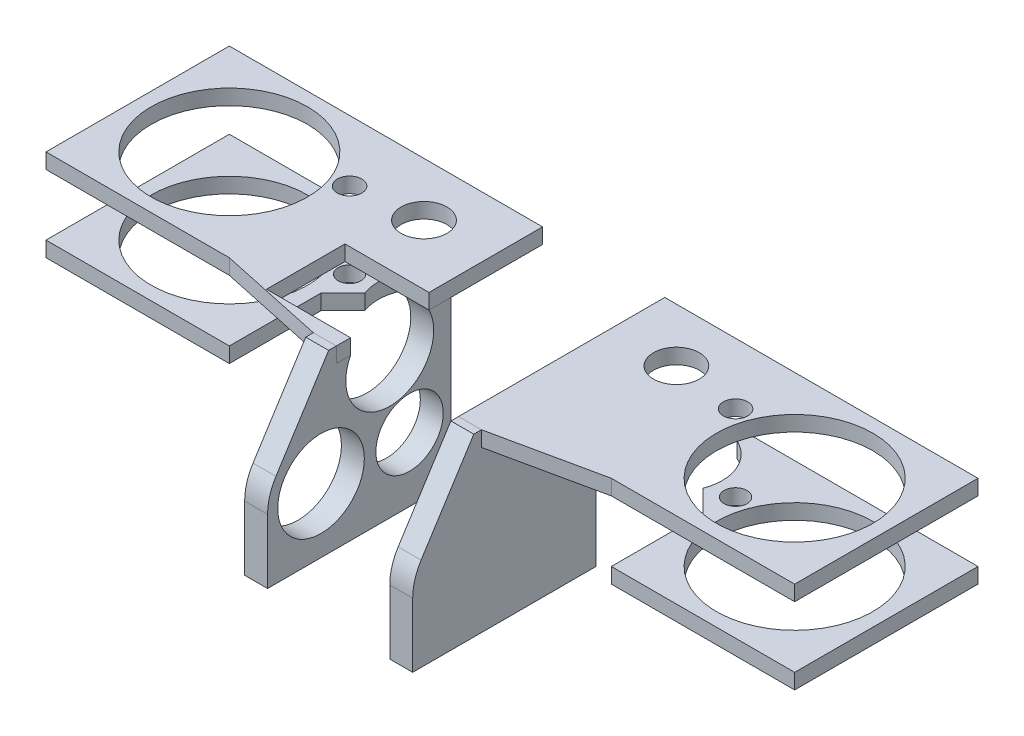
SolidWorks part; units mm, degrees
material "Alum Plate"
ref_plane "Front Plane" through (0, 0, 0) normal (0, 0, 1) x (1, 0, 0)
ref_plane "Top Plane" through (0, 0, 0) normal (0, 1, 0) x (1, 0, 0)
ref_plane "Right Plane" through (0, 0, 0) normal (1, 0, 0) x (0, 0, -1)
sketch "Sketch1" plane through (0, 0, 0) normal (0, 1, 0) x (1, 0, 0)
  line L0 (0, 0) -> (117.475, 0) construction
  line L1 (-117.475, 0) -> (0, 0) construction
  line L3 (-9.525, 158.75) -> (-3.175, 158.75)
  line L4 (-9.525, 158.75) -> (-9.525, 44.45)
  line L5 (-9.525, 44.45) -> (-3.175, 44.45)
  line L6 (-3.175, 158.75) -> (-3.175, 44.45)
  line L7 (-9.525, 158.75) -> (-3.175, 44.45) construction
  line L8 (-9.525, 44.45) -> (-3.175, 158.75) construction
  line L14 (-155.575, -76.2) -> (155.575, -76.2)
  line L18 (-117.475, 0) -> (-52.4506, 15.875) construction
  line L19 (52.4506, 15.875) -> (117.475, 0) construction
  line L20 (-25.4, 38.1) -> (0, 38.1) construction
  line L21 (-6.35, 101.6) -> (0, 101.6)
  line L29 (0, 0) -> (0, -25.4) construction
  line L30 (-117.475, 0) -> (-80.2096, 12.7) construction
  line L43 (-80.2096, 12.7) -> (-52.4506, 15.875) construction
  line L44 (52.4506, 15.875) -> (80.2096, 12.7) construction
  line L55 (80.2096, 12.7) -> (117.475, 0) construction
  line L69 (-155.575, -76.2) -> (-155.575, 38.1)
  line L70 (-155.575, 38.1) -> (155.575, 38.1)
  line L71 (155.575, -76.2) -> (155.575, 38.1)
  line L78 (0, 101.6) -> (0, -25.4)
  line L79 (0, -25.4) -> (0, -152.4) construction
  line L80 (-9.525, -209.55) -> (-3.175, -209.55) construction
  line L81 (-9.525, -209.55) -> (-9.525, -95.25) construction
  line L82 (-9.525, -95.25) -> (-3.175, -95.25) construction
  line L83 (-3.175, -209.55) -> (-3.175, -95.25) construction
  line L84 (-9.525, -209.55) -> (-3.175, -95.25) construction
  line L85 (-9.525, -95.25) -> (-3.175, -209.55) construction
  line L86 (0, -152.4) -> (-6.35, -152.4) construction
  line L87 (-34.925, -76.2) -> (-25.4, -76.2)
  line L88 (-34.925, -76.2) -> (-34.925, 38.1)
  line L89 (-34.925, 38.1) -> (-25.4, 38.1)
  line L90 (-25.4, -76.2) -> (-25.4, 38.1)
  line L91 (34.925, -76.2) -> (25.4, -76.2)
  line L92 (34.925, -76.2) -> (34.925, 38.1)
  line L93 (34.925, 38.1) -> (25.4, 38.1)
  line L94 (25.4, -76.2) -> (25.4, 38.1)
  line L95 (0, 38.1) -> (25.4, 38.1) construction
  circle A0 centre (-117.475, 0) radius 32.5
  circle A1 centre (-117.475, 0) radius 25
  circle A2 centre (117.475, 0) radius 32.5
  circle A3 centre (117.475, 0) radius 25
  circle A4 centre (-52.4506, 15.875) radius 17.5006
  circle A5 centre (52.4506, 15.875) radius 17.5006
  circle A6 centre (-80.2096, 12.7) radius 22.86
  circle A7 centre (80.2096, 12.7) radius 22.86
  point P8 (-6.35, 101.6)
  point P21 (117.475, 32.5)
  point P25 (52.4506, 33.3756)
  point P29 (52.4506, -1.6256)
  point P31 (0, -76.2)
  point P32 (-6.35, -152.4)
  point P62 (149.975, 0)
  dimension "D1" = 50
  dimension "D2" = 65
  dimension "D8" = 35.0012
  dimension "D11" = 127
  dimension "D12" = 63.5
  dimension "D17" = 45.72
  dimension "D3" = 114.3
  dimension "D4" = 6.35
  dimension "D5" = 234.95
  dimension "D6" = 38.1
  dimension "D7" = 38.1
  dimension "D9" = 114.3
  dimension "D10" = 9.525
  dimension "D13" = 9.525
  dimension "D14" = 50.8
  dimension "D15" = 27.94
  dimension "D16" = 39.37
  dimension "D18" = 22.225
  dimension "D19" = 25.4
sketch "Sketch2" plane through (0, 0, 0) normal (1, 0, 0) x (0, 0, -1)
  line L0 (0, 22.225) -> (0, 49.825) construction
  line L1 (-32.5, 53.325) -> (32.5, 53.325)
  line L2 (-32.5, 53.325) -> (-32.5, 46.325)
  line L3 (-32.5, 46.325) -> (32.5, 46.325)
  line L4 (32.5, 53.325) -> (32.5, 46.325)
  line L5 (-32.5, 53.325) -> (32.5, 46.325) construction
  line L6 (-32.5, 46.325) -> (32.5, 53.325) construction
  line L7 (-32.5, 82.55) -> (32.5, 82.55)
  line L8 (-32.5, 82.55) -> (-32.5, 75.55)
  line L9 (-32.5, 75.55) -> (32.5, 75.55)
  line L10 (32.5, 82.55) -> (32.5, 75.55)
  line L11 (-32.5, 82.55) -> (32.5, 75.55) construction
  line L12 (-32.5, 75.55) -> (32.5, 82.55) construction
  line L13 (-25.8191, 0) -> (33.9817, 0) construction
  line L14 (-25.4, 69.85) -> (-152.4, 69.85)
  line L15 (-76.2, 84.425) -> (38.1, 84.425)
  line L16 (-76.2, 84.425) -> (-76.2, 46.325)
  line L17 (-76.2, 46.325) -> (38.1, 46.325)
  line L18 (38.1, 84.425) -> (38.1, 46.325)
  line L19 (-17.175, 38.1) -> (-53.975, 38.1) construction
  line L20 (-53.975, 38.1) -> (-25.4, 69.85) construction
  line L21 (101.6, 0) -> (-25.4, 0) construction
  line L22 (-76.2, 78.075) -> (38.1, 78.075)
  line L23 (-76.2, 52.675) -> (38.1, 52.675)
  line L24 (-17.175, 38.1) -> (-25.4, 69.85) construction
  line L25 (-3.175, 38.1) -> (-3.175, 75.55) construction
  line L32 (-76.2, 11.4) -> (38.1, 11.4)
  line L33 (-76.2, 11.4) -> (-76.2, 8.225)
  line L38 (-76.2, 8.225) -> (38.1, 8.225)
  line L39 (38.1, 11.4) -> (38.1, 8.225)
  line L40 (-1.6256, 33.5742) -> (33.3756, 33.5742)
  line L41 (-1.6256, 33.5742) -> (-1.6256, 78.075)
  line L42 (-1.6256, 78.075) -> (33.3756, 78.075)
  line L43 (33.3756, 33.5742) -> (33.3756, 78.075)
  line L44 (-1.6256, 33.5742) -> (33.3756, 78.075) construction
  line L45 (-1.6256, 78.075) -> (33.3756, 33.5742) construction
  line L46 (-38.1, 84.425) -> (-38.1, 46.325)
  line L47 (-38.1, 65.375) -> (0, 65.375) construction
  line L48 (0, 65.375) -> (38.1, 65.375) construction
  line L49 (-76.2, 11.4) -> (38.1, 8.225) construction
  line L50 (-76.2, 8.225) -> (38.1, 11.4) construction
  circle A0 centre (0, 22.225) radius 22.225
  circle A1 centre (-25.4, 69.85) radius 18.0086
  circle A2 centre (-17.175, 38.1) radius 14
  circle A3 centre (-152.4, 69.85) radius 57.15
  circle A4 centre (-25.4, 69.85) radius 4.7625
  circle A5 centre (-53.975, 38.1) radius 18
  point P2 (0, 49.825)
  point P8 (0, 79.05)
  point P16 (-35.975, 38.1)
  point P28 (-71.975, 38.1)
  point P32 (15.875, 55.8246)
  point P34 (-209.55, 69.85)
  point P35 (-31.175, 38.1)
  point P36 (-3.175, 38.1)
  point P37 (-7.3914, 69.85)
  point P38 (-43.4086, 69.85)
  point P47 (-17.175, 31.4669)
  point P55 (38.1, 83.895)
  point P57 (-19.05, 9.8125)
  dimension "D1" = 44.45
  dimension "D8" = 36.0172
  dimension "D2" = 28
  dimension "D11" = 9.525
  dimension "D12" = 36
  dimension "D3" = 7
  dimension "D4" = 82.55
  dimension "D5" = 22.225
  dimension "D6" = 6.35
  dimension "D7" = 6.35
  dimension "D9" = 69.85
  dimension "D10" = 44.5008
  dimension "D13" = 19.05
  dimension "D14" = 28.575
  dimension "D15" = 3.175
  dimension "D16" = 25.4
  dimension "D17" = 31.75
  dimension "D18" = 34.925
sketch "Sketch5" plane through (0, 0, 0) normal (0, 1, 0) x (1, 0, 0)
  line L0 (-34.925, -76.2) -> (-34.925, 38.1) construction
  line L1 (-60.071, -3.175) -> (-28.575, -3.175)
  line L2 (-60.071, -3.175) -> (-60.071, -31.175)
  line L3 (-60.071, -31.175) -> (-28.575, -31.175)
  line L4 (-28.575, -3.175) -> (-28.575, -31.175)
  line L5 (-60.071, -3.175) -> (-28.575, -31.175) construction
  line L6 (-60.071, -31.175) -> (-28.575, -3.175) construction
  line L7 (-74.93, -35.975) -> (-34.925, -35.975)
  line L8 (-74.93, -35.975) -> (-74.93, -71.975)
  line L9 (-74.93, -71.975) -> (-34.925, -71.975)
  line L10 (-34.925, -35.975) -> (-34.925, -71.975)
  line L11 (-74.93, -35.975) -> (-34.925, -71.975) construction
  line L12 (-74.93, -71.975) -> (-34.925, -35.975) construction
  line L13 (-60.071, -7.3914) -> (-20.066, -7.3914)
  line L14 (-60.071, -7.3914) -> (-60.071, -43.4086)
  line L15 (-60.071, -43.4086) -> (-20.066, -43.4086)
  line L16 (-20.066, -7.3914) -> (-20.066, -43.4086)
  line L17 (-60.071, -7.3914) -> (-20.066, -43.4086) construction
  line L18 (-60.071, -43.4086) -> (-20.066, -7.3914) construction
  line L20 (-25.4, -76.2) -> (-25.4, 38.1) construction
  point P0 (-44.323, -17.175)
  point P5 (-54.9275, -53.975)
  point P10 (-40.0685, -25.4)
  dimension "D1" = 3.175
  dimension "D2" = 31.496
  dimension "D5" = 40.005
  dimension "D6" = 40.005
ref_plane "Plane1" through (0, 78.075, 0) normal (0, 1, 0) x (1, 0, 0)
ref_plane "Plane2" through (0, 52.675, 0) normal (0, -1, 0) x (-1, 0, 0)
ref_plane "Plane3" through (25.4, 0, 0) normal (1, 0, 0) x (0, 0, -1)
sketch "Sketch6" plane through (25.4, 0, 0) normal (1, 0, 0) x (0, 0, -1)
  line L2 (-72.7158, 50.0472) -> (-50.8, 84.425)
  line L3 (-76.2, 84.425) -> (38.1, 84.425) construction
  line L4 (-50.8, 84.425) -> (-47.625, 84.425)
  line L5 (-47.625, 84.425) -> (-47.625, 78.075)
  line L6 (-76.2, 78.075) -> (38.1, 78.075) construction
  line L7 (-47.625, 78.075) -> (0, 78.075)
  line L8 (0, 78.075) -> (0, 11.4)
  line L10 (-76.2, 11.4) -> (38.1, 11.4) construction
  line L11 (-76.2, 11.4) -> (-76.2, 38.1)
  line L12 (-76.2, 11.4) -> (0, 11.4)
  arc A3 (-76.2, 38.1) -> (-72.7158, 50.0472) centre (-53.975, 38.1) cw
  dimension "D1" = 25.4
  dimension "D2" = 22.225
  dimension "D3" = 3.175
extrude "Boss-Extrude1" add sketch "Sketch6" along normal up to vertex (9.525 mm away) up to point (34.925, 0, -38.1)
sketch "Sketch7" plane through (0, 78.075, 0) normal (0, 1, 0) x (1, 0, 0)
  line L0 (25.4, -47.625) -> (34.925, -47.625)
  line L2 (155.575, -76.2) -> (155.575, 38.1) construction
  line L3 (155.575, -38.1) -> (155.575, 38.1)
  line L4 (155.575, 38.1) -> (25.4, 38.1)
  line L5 (25.4, 38.1) -> (25.4, -47.625)
  line L6 (155.575, -38.1) -> (79.375, -38.1)
  line L7 (79.375, -38.1) -> (34.925, -47.625)
  line L8 (117.475, 38.1) -> (117.475, 0) construction
  line L9 (117.475, 0) -> (117.475, -38.1) construction
  circle A0 centre (117.475, 0) radius 32.5 construction
  circle A1 centre (117.475, 0) radius 32.5
  circle A2 centre (80.2096, 12.7) radius 5.08
  circle A3 centre (52.4506, 15.875) radius 9.525
  dimension "D1" = 10.16
  dimension "D2" = 19.05
extrude "Boss-Extrude2" add sketch "Sketch7" along normal up to surface (6.35 mm away) separate body up to face at (30.1625, 84.425, 49.2125)
sketch "Sketch8" plane through (0, 52.675, 0) normal (0, -1, 0) x (-1, 0, 0)
  line L0 (-60.325, 33.2214) -> (-60.325, 38.1)
  line L1 (-79.375, -38.1) -> (-155.575, -38.1)
  line L2 (-79.375, -38.1) -> (-79.375, 38.1) construction
  line L3 (-79.375, 38.1) -> (-155.575, 38.1)
  line L4 (-155.575, -38.1) -> (-155.575, 38.1)
  line L5 (-79.375, -38.1) -> (-155.575, 38.1) construction
  line L6 (-79.375, 38.1) -> (-155.575, -38.1) construction
  line L7 (155.575, 38.1) -> (-155.575, 38.1) construction
  line L8 (-60.325, 38.1) -> (-79.375, 38.1)
  line L9 (-79.375, -38.1) -> (-79.375, 0)
  line L10 (-79.375, 0) -> (-70.2606, 9.1144)
  line L11 (-34.925, -76.2) -> (-34.925, 38.1) construction
  circle A0 centre (-117.475, 0) radius 32.5 construction
  circle A1 centre (-117.475, 0) radius 32.5
  arc A2 (-70.2606, 9.1144) -> (-60.325, 33.2214) centre (-52.4506, 15.875) cw
  circle A3 centre (-80.2096, 12.7) radius 4.7625
  dimension "D1" = 9.525
  dimension "D2" = 19.05
  dimension "D3" = 25.4
  dimension "D4" = 45
  dimension "D5" = 38.1
extrude "Boss-Extrude3" add sketch "Sketch8" along normal up to vertex (6.35 mm away) separate body up to point (0, 46.325, -38.1)
mirror "Mirror2" about plane through (0, 0, 0) normal (1, 0, 0) of bodies 106 108 111
sketch "Sketch10" plane through (-25.4, 0, 0) normal (1, 0, 0) x (0, 0, -1)
  circle A0 centre (-53.975, 38.1) radius 18 construction
  circle A1 centre (-53.975, 38.1) radius 18
  circle A2 centre (-17.175, 38.1) radius 14 construction
  circle A3 centre (-17.175, 38.1) radius 14
extrude "Cut-Extrude2" cut sketch "Sketch10" against normal through all
sketch "Sketch11" plane through (-34.925, 0, 0) normal (-1, 0, 0) x (0, 0, 1)
  circle A1 centre (25.4, 69.85) radius 18.2626
  circle A4 centre (25.4, 69.85) radius 18.0086 construction
  dimension "D1" = 0.254
extrude "Cut-Extrude6" cut sketch "Sketch11" against normal through all
sketch "Sketch12" plane through (0, 78.075, 0) normal (0, -1, 0) x (1, 0, 0)
  line L0 (-60.071, 7.3914) -> (-60.071, 43.4086) construction
  line L1 (-25.4, 9.0944) -> (-60.325, 9.0944)
  line L2 (-25.4, 9.0944) -> (-25.4, 41.7056)
  line L3 (-25.4, 41.7056) -> (-60.325, 41.7056)
  line L4 (-60.325, 9.0944) -> (-60.325, 41.7056)
  line L5 (-25.4, 9.0944) -> (-60.325, 41.7056) construction
  line L6 (-25.4, 41.7056) -> (-60.325, 9.0944) construction
  line L7 (-25.4, -38.1) -> (-25.4, 47.625) construction
  point P4 (-42.8625, 25.4)
  point P5 (0, 0)
  point P6 (0, 0)
  point P7 (-25.4, 16.438)
  dimension "D1" = 0.254
extrude "Cut-Extrude7" cut sketch "Sketch12" against normal through all
